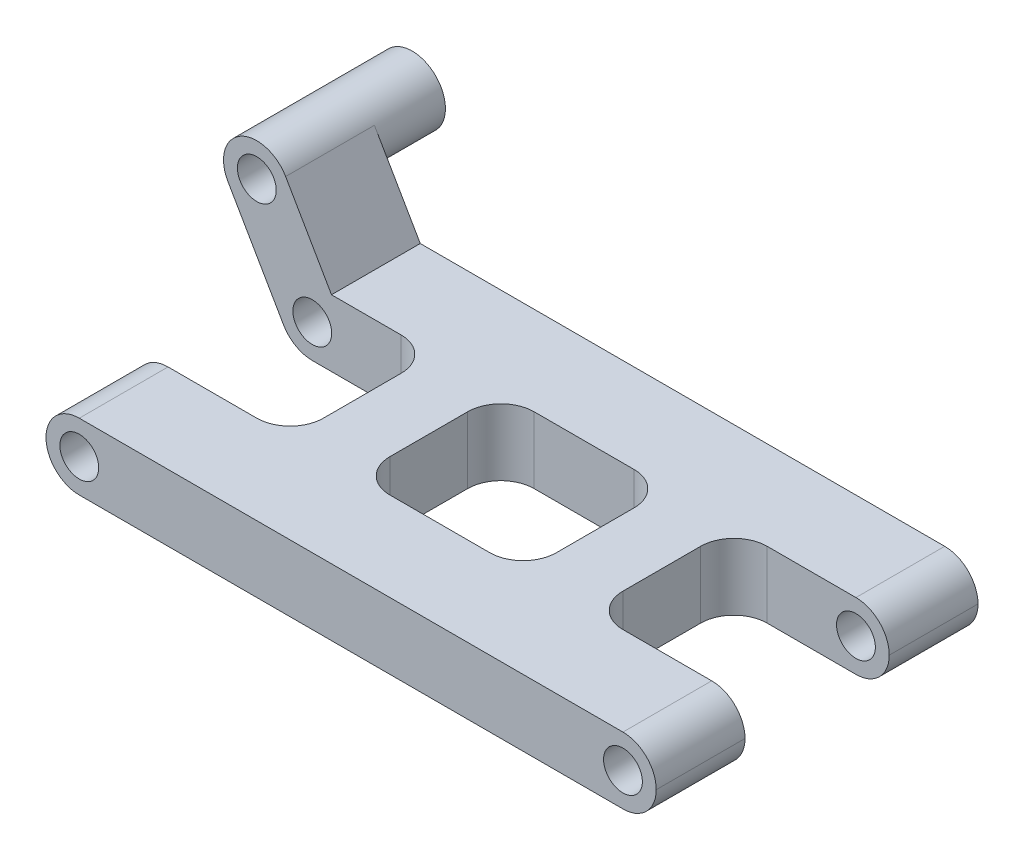
SolidWorks part; units mm, degrees
ref_plane "Alzado" through (0, 0, 0) normal (0, 0, 1) x (1, 0, 0)
ref_plane "Planta" through (0, 0, 0) normal (0, 1, 0) x (1, 0, 0)
ref_plane "Vista lateral" through (0, 0, 0) normal (1, 0, 0) x (0, 0, -1)
sketch "Croquis1" plane through (0, 0, 0) normal (0, 1, 0) x (1, 0, 0)
  line L0 (0, 0) -> (0, 8)
  line L1 (0, 8) -> (14, 8)
  line L2 (14, 8) -> (14, 21)
  line L3 (14, 21) -> (0, 21)
  line L4 (0, 21) -> (0, 29)
  line L16 (0, 29) -> (55, 29)
  line L17 (55, 29) -> (55, 21)
  line L18 (14, 14.5) -> (48, 14.5) construction
  line L22 (55, 0) -> (55, 8)
  line L23 (55, 8) -> (41, 8)
  line L24 (55, 21) -> (41, 21)
  line L25 (41, 21) -> (41, 8)
  line L26 (0, 0) -> (55, 0)
  line L27 (20, 8) -> (35, 8)
  line L28 (20, 8) -> (20, 21)
  line L29 (20, 21) -> (35, 21)
  line L30 (35, 8) -> (35, 21)
  dimension "D1" = 8
  dimension "D2" = 13
  dimension "D3" = 8
  dimension "D4" = 55
  dimension "D5" = 8
  dimension "D6" = 14
  dimension "D7" = 15
  dimension "D8" = 55
  dimension "D9" = 14
  dimension "D10" = 8
  dimension "D11" = 13
  dimension "D12" = 6
  dimension "D13" = 6
extrude "Saliente-Extruir1" add sketch "Croquis1" along normal mid plane 6
fillet "Redondeo1" radius 3 8 edges at (0, -3, -4) (0, 3, -4) (0, -3, -25) (0, 3, -25) (55, -3, -4) (55, 3, -4) (55, 3, -25) (55, -3, -25)
sketch "Croquis2" plane through (0, 0, 0) normal (0, 0, 1) x (1, 0, 0)
  circle A0 centre (3, 0) radius 1.75
  dimension "D1" = 3.5
extrude "Cortar-Extruir1" cut sketch "Croquis2" against normal through all both and the other way through all
sketch "Croquis3" plane through (0, 0, 0) normal (0, 0, 1) x (1, 0, 0)
  line L1 (3, -3) -> (52, -3) construction
  circle A0 centre (52, 0) radius 1.75
  dimension "D1" = 3.5
  dimension "D2" = 3
  dimension "D3" = 3
extrude "Cortar-Extruir2" cut sketch "Croquis3" against normal through all both
fillet "Redondeo2" radius 3 8 edges at (14, 0, -8) (35, 0, -8) (20, 0, -8) (41, 0, -8) (41, 0, -21) (20, 0, -21) (14, 0, -21) (35, 0, -21)
ref_axis "Eje1" through (3, 0, -8) along (0, 0, 1)
ref_plane "Plano1" through (2.25, 1.299, 0) normal (-0.866, -0.5, 0) x (0, 0, 1)
sketch "Croquis5" plane through (0, 0, 0) normal (0, 0, 1) x (1, 0, 0)
  line L0 (0.5981, 10.1603) -> (5.5981, 1.5)
  line L1 (-4.5981, 7.1603) -> (0.4019, -1.5)
  line L2 (-2, 8.6603) -> (3, 0) construction
  arc A0 (0.4019, -1.5) -> (5.5981, 1.5) centre (3, 0) ccw
  circle A2 centre (-2, 8.6603) radius 1.75
  circle A3 centre (3, 0) radius 1.75
  arc A4 (0.5981, 10.1603) -> (-4.5981, 7.1603) centre (-2, 8.6603) ccw
  dimension "D2" = 3.5
  dimension "D3" = 120
  dimension "D4" = 10
extrude "Saliente-Extruir2" add sketch "Croquis5" against normal blind 8 from surface starting at face at (1.25, 0, -21)
sketch "Croquis6" plane through (0, 0, 0) normal (0, 0, 1) x (1, 0, 0)
  circle A0 centre (-2, 8.6603) radius 1.75
  circle A1 centre (-2, 8.6603) radius 3
extrude "Saliente-Extruir3" add sketch "Croquis6" against normal blind 6 from surface starting at face at (20.3345, 2.2588, -29)
